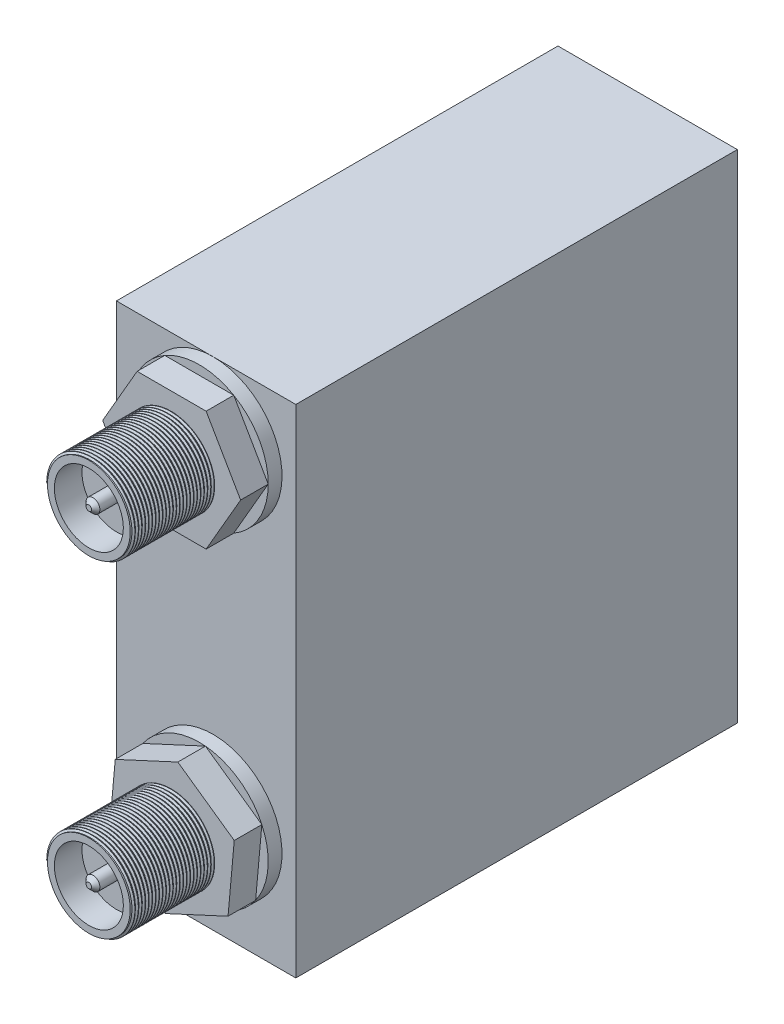
SolidWorks part; units mm, degrees
ref_plane "Front Plane" through (0, 0, 0) normal (0, 0, 1) x (1, 0, 0)
ref_plane "Top Plane" through (0, 0, 0) normal (0, 1, 0) x (1, 0, 0)
ref_plane "Right Plane" through (0, 0, 0) normal (1, 0, 0) x (0, 0, -1)
sketch "Sketch1" plane through (0, 0, 0) normal (0, 1, 0) x (1, 0, 0)
  line L1 (-6.5, -16) -> (6.5, -16)
  line L2 (-6.5, -16) -> (-6.5, 16)
  line L3 (-6.5, 16) -> (6.5, 16)
  line L4 (6.5, -16) -> (6.5, 16)
  line L5 (-6.5, -16) -> (6.5, 16) construction
  line L6 (-6.5, 16) -> (6.5, -16) construction
  point P0 (0, 0)
  dimension "D1" = 13
  dimension "D2" = 32
extrude "Boss-Extrude1" add sketch "Sketch1" along normal blind 36
sketch "Sketch2" plane through (0, 0, 16) normal (0, 0, 1) x (1, 0, 0)
  line L0 (-6.5, 36) -> (6.5, 36) construction
  line L1 (6.5, 36) -> (6.5, 0) construction
  line L2 (-6.5, 0) -> (6.5, 0) construction
  circle A0 centre (0.5, 31) radius 5
  circle A1 centre (0.5, 7.3) radius 5
  dimension "D1" = 10
  dimension "D3" = 6
  dimension "D4" = 10
  dimension "D5" = 6
  dimension "D6" = 7.3
  dimension "D2" = 5
extrude "Boss-Extrude2" add sketch "Sketch2" along normal blind 1
sketch "Sketch3" plane through (0, 0, 17) normal (0, 0, 1) x (1, 0, 0)
  line L1 (5.5, 31) -> (3, 35.3301)
  line L2 (3, 35.3301) -> (-2, 35.3301)
  line L3 (-2, 35.3301) -> (-4.5, 31)
  line L4 (-4.5, 31) -> (-2, 26.6699)
  line L5 (-2, 26.6699) -> (3, 26.6699)
  line L6 (3, 26.6699) -> (5.5, 31)
  line L7 (5.0373, 9.4006) -> (0.9495, 12.2798)
  line L8 (0.9495, 12.2798) -> (-3.5878, 10.1792)
  line L9 (-3.5878, 10.1792) -> (-4.0373, 5.1994)
  line L10 (-4.0373, 5.1994) -> (0.0505, 2.3202)
  line L11 (0.0505, 2.3202) -> (4.5878, 4.4208)
  line L12 (4.5878, 4.4208) -> (5.0373, 9.4006)
  circle A0 centre (0.5, 31) radius 4.3301 construction
  circle A1 centre (0.5, 7.3) radius 4.3301 construction
extrude "Boss-Extrude3" add sketch "Sketch3" along normal blind 2
sketch "Sketch4" plane through (0, 0, 19) normal (0, 0, 1) x (1, 0, 0)
  circle A0 centre (0.5, 31) radius 3
  circle A1 centre (0.5, 7.3) radius 3
  dimension "D1" = 6
  dimension "D2" = 6
extrude "Boss-Extrude4" add sketch "Sketch4" along normal blind 6
sketch "Sketch5" plane through (0, 0, 25) normal (0, 0, 1) x (1, 0, 0)
  circle A2 centre (0.5, 31) radius 2.5
  circle A3 centre (0.5, 31) radius 2.5
  circle A8 centre (0.5, 7.3) radius 0.5
  circle A9 centre (0.5, 7.3) radius 0.5
  circle A11 centre (0.5, 7.3) radius 2.5
  circle A12 centre (0.5, 7.3) radius 2.5
  circle A14 centre (0.5, 31) radius 0.5
  circle A15 centre (0.5, 31) radius 0.5
  dimension "D1" = 0.5
  dimension "D2" = 0.5
  dimension "D3" = 2.5
  dimension "D4" = 2.5
extrude "Cut-Extrude2" cut sketch "Sketch5" against normal blind 2
chamfer "Chamfer1" distance 0.3 angle 45 2 edges at (1, 7.3, 25) (1, 31, 25)
thread "Thread1" pitch 0.25 start angle 0, offset 0, length 6, pitch 0.25, diameter 6
ref_plane "Plane1" through (-2.5, 31, 25) normal (0, -1, 0) x (-1, 0, 0)
sketch "Thread Profile1" plane through (-2.5, 31, 25) normal (0, -1, 0) x (-1, 0, 0)
  line L0 (0, 0) -> (0, 0.25) construction
  line L1 (0, 0) -> (0.1353, 0.0781)
  line L2 (0.1353, 0.0781) -> (0.1353, 0.1094)
  line L3 (0.1353, 0.1094) -> (0, 0.1875)
  line L4 (0.1353, 0.0937) -> (0, 0.0937) construction
  line L11 (0, 0) -> (0, 0.1875)
  point P2 (0, 0)
  dimension "Pitch" = 0.25
  dimension "Profile_Angle" = 60
  dimension "Profile_Land" = 0.0312
  dimension "Profile_Height" = 0.1353
thread "Thread2" pitch 0.25 profile "Thread Profile2" start angle 0, offset 0, length 6, pitch 0.25, diameter 6
ref_plane "Plane2" through (-2.5, 7.3, 25) normal (0, -1, 0) x (-1, 0, 0)
sketch "Thread Profile2" plane through (-2.5, 7.3, 25) normal (0, -1, 0) x (-1, 0, 0)
  line L0 (0, 0) -> (0, 0.25) construction
  line L1 (0, 0) -> (0.1353, 0.0781)
  line L2 (0.1353, 0.0781) -> (0.1353, 0.1094)
  line L3 (0.1353, 0.1094) -> (0, 0.1875)
  line L4 (0.1353, 0.0937) -> (0, 0.0937) construction
  line L11 (0, 0) -> (0, 0.1875)
  point P2 (0, 0)
  dimension "Pitch" = 0.25
  dimension "Profile_Angle" = 60
  dimension "Profile_Land" = 0.0312
  dimension "Profile_Height" = 0.1353
